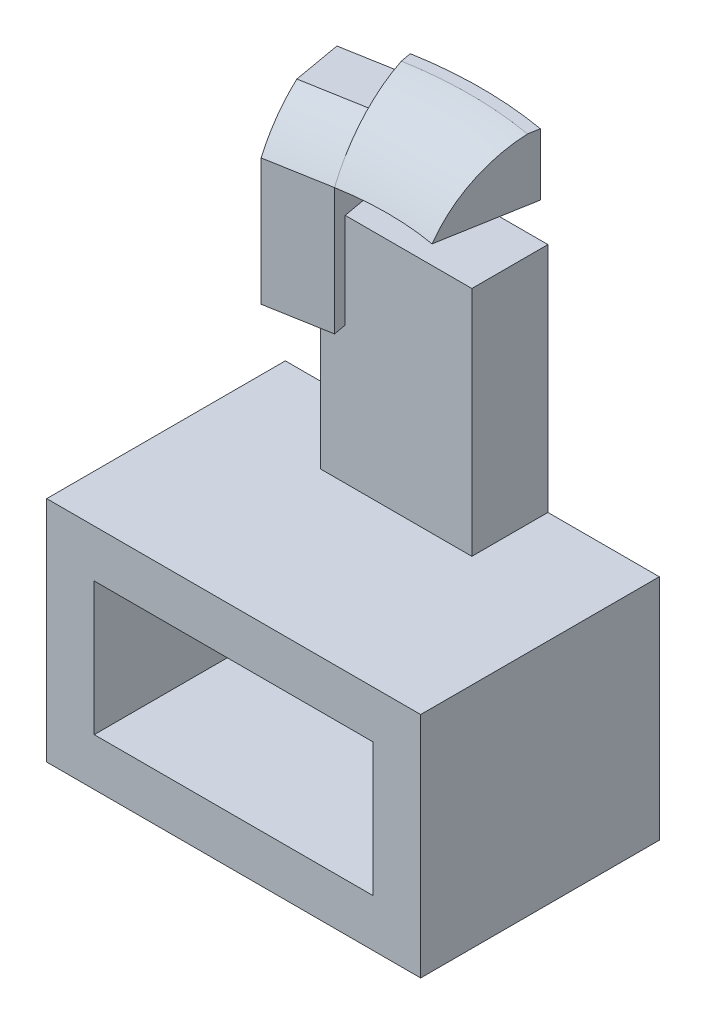
SolidWorks part; units mm, degrees
note: The reader was unsure of these and kept them because the rebuilt part matched: shared geometry of "Sketch3<2>", "Sketch3<4>", "Sketch3<5>".
ref_plane "Front Plane" through (0, 0, 0) normal (0, 0, 1) x (1, 0, 0)
ref_plane "Top Plane" through (0, 0, 0) normal (0, 1, 0) x (1, 0, 0)
ref_plane "Right Plane" through (0, 0, 0) normal (1, 0, 0) x (0, 0, -1)
sketch "Sketch3" plane through (0, 0, 0) normal (0, 0, 1) x (1, 0, 0)
  line L1 (22, -10.5) -> (-22, -10.5)
  line L2 (22, -10.5) -> (22, 10.5)
  line L3 (22, 10.5) -> (-22, 10.5)
  line L4 (-22, -10.5) -> (-22, 10.5)
  line L5 (22, -10.5) -> (-22, 10.5) construction
  line L6 (22, 10.5) -> (-22, -10.5) construction
  line L7 (-29.5, 18) -> (29.5, 18)
  line L8 (-29.5, 18) -> (-29.5, -18)
  line L9 (-29.5, -18) -> (29.5, -18)
  line L10 (29.5, 18) -> (29.5, -18)
  point P0 (0, 0)
  dimension "D1" = 44
  dimension "D2" = 21
  dimension "D3" = 7.5
  dimension "D4" = 7.5
  dimension "D5" = 7.5
  dimension "D6" = 7.5
extrude "Boss-Extrude1" add sketch "Sketch3" along normal blind 10
extrude "Boss-Extrude2" add sketch "Sketch3<2>" against normal blind 5 contours L4 L1 L2 L3 | L10 L7 L8 L9 L1 L4 L3 L2
sketch "Sketch3<2>" plane through (0, 0, 0) normal (0, 0, 1) x (1, 0, 0) same geometry as "Sketch3"
sketch "Sketch4" plane through (0, 18, 0) normal (0, 1, 0) x (1, 0, 0)
  line L0 (0, 23.7678) -> (0, -28.5593) construction
  line L1 (-29.5, 5) -> (29.5, 5) construction
  line L3 (11.9276, -7) -> (-11.9276, -7)
  line L4 (11.9276, -7) -> (11.9276, 5)
  line L5 (11.9276, 5) -> (-11.9276, 5)
  line L6 (-11.9276, -7) -> (-11.9276, 5)
  line L7 (11.9276, -7) -> (-11.9276, 5) construction
  line L8 (11.9276, 5) -> (-11.9276, -7) construction
  point P5 (0, 5)
  point P6 (0, -1)
  dimension "D1" = 12
extrude "Boss-Extrude3" add sketch "Sketch4" along normal blind 36.6
sketch "Sketch5" plane through (0, 0, 0) normal (1, 0, 0) x (0, 0, -1)
  line L0 (-1, 169.0786) -> (-1, -49.8786) construction
  line L1 (-7, 54.6) -> (5, 54.6) construction
  line L2 (6.375, 59.6) -> (-8.375, 59.6)
  line L3 (5, 54.6) -> (-7, 54.6) construction
  line L4 (6.375, 59.6) -> (6.375, 69.35)
  line L5 (6.375, 69.35) -> (4.625, 69.35)
  arc A0 (-8.375, 59.6) -> (4.625, 69.35) centre (8.9258, 50.074) cw
  point P2 (-1, 59.6)
  point P5 (-1, 54.6)
  dimension "D3" = 9.75
  dimension "D5" = 19.75
  dimension "D1" = 5
  dimension "D2" = 14.75
  dimension "D4" = 1.75
sketch "Sketch6" plane through (0, 0, 0) normal (1, 0, 0) x (0, 0, -1)
  line L0 (-52.68, -41.3963) -> (-52.68, 69.3281)
  line L1 (-1, 169.0786) -> (-1, -49.8786) construction
  dimension "D1" = 51.68
revolve "Revolve1" add sketch "Sketch5" angle 20 mid plane about L0
sketch "Sketch7" plane through (-9.0088, 0, 1.5885) normal (0.9848, 0, -0.1736) x (-0.1736, 0, -0.9848)
  line L1 (7.1753, 59.6) -> (7.1753, 66.344)
  line L2 (7.1753, 66.344) -> (-0.6141, 66.344)
  line L3 (7.1753, 59.6) -> (7.1753, 39.6)
  line L4 (7.1753, 39.6) -> (-7.5747, 39.6)
  line L5 (-7.5747, 39.6) -> (-7.5747, 59.6)
  line L6 (2.8528, 54.6) -> (6.9952, 54.6) construction
  arc A0 (-0.6141, 66.344) -> (-7.5747, 59.6) centre (8.3881, 50.0886) ccw
  line M12 (7.1753, 59.6) -> (-7.5747, 59.6)
  arc M13 (-7.5747, 59.6) -> (5.4253, 69.35) centre (9.7261, 50.074) cw
  dimension "D1" = 15
extrude "Boss-Extrude4" add sketch "Sketch7" against normal blind 10 contours L4 L5 L3 M12 | L1 M12 M13
sketch "Sketch9" plane through (-11.9276, 0, 0) normal (1, 0, 0) x (0, 0, -1)
  line L0 (-7, 44.3348) -> (-7, 54.6)
  line L2 (-7, 54.6) -> (5, 54.6)
  line L3 (5, 54.6) -> (5, 44.3348)
  line L4 (5, 44.3348) -> (-7, 44.3348)
  line L5 (5, 54.6) -> (5, 18) construction
  line L6 (-7, 54.6) -> (-7, 18) construction
  line L7 (-7, 54.6) -> (5, 54.6) construction
extrude "Boss-Extrude5" add sketch "Sketch9" against normal up to surface (1.757 mm away)
extrude "Boss-Extrude6" add sketch "Sketch3<4>" along normal blind 7.65 contours L4 L1 L2 L3 | L10 L7 L8 L9 L1 L4 L3 L2
sketch "Sketch3<4>" plane through (0, 0, 0) normal (0, 0, 1) x (1, 0, 0) same geometry as "Sketch3"
extrude "Boss-Extrude7" add sketch "Sketch3<5>" along normal blind 25 from surface at 7.65 starting at face at (0, 0, 7.65)
sketch "Sketch3<5>" plane through (0, 0, 0) normal (0, 0, 1) x (1, 0, 0) same geometry as "Sketch3"
